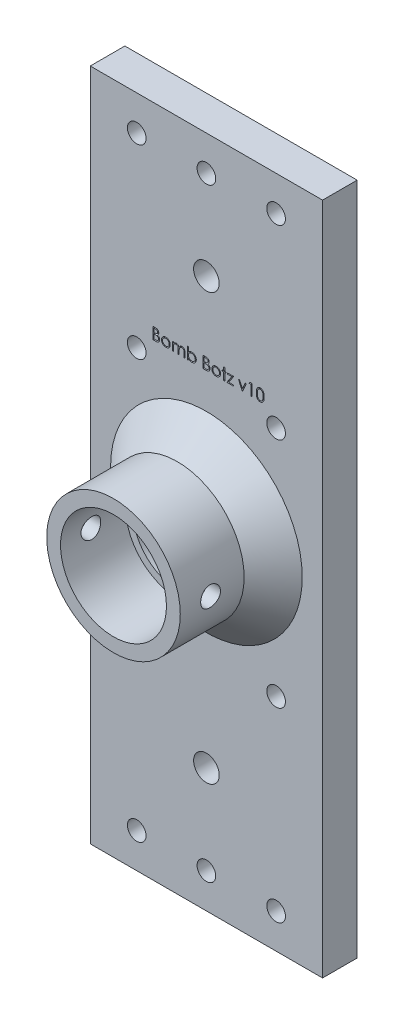
SolidWorks part; units mm, degrees
ref_plane "Front Plane" through (0, 0, 0) normal (0, 0, 1) x (1, 0, 0)
ref_plane "Top Plane" through (0, 0, 0) normal (0, 1, 0) x (1, 0, 0)
ref_plane "Right Plane" through (0, 0, 0) normal (1, 0, 0) x (0, 0, -1)
sketch "Sketch1" plane through (0, 0, 0) normal (0, 0, 1) x (1, 0, 0)
  line L5 (-31.75, 92.075) -> (31.75, 92.075)
  line L6 (-31.75, 92.075) -> (-31.75, -92.075)
  line L7 (-31.75, -92.075) -> (31.75, -92.075)
  line L8 (31.75, 92.075) -> (31.75, -92.075)
  line L9 (-31.75, 92.075) -> (31.75, -92.075) construction
  line L10 (-31.75, -92.075) -> (31.75, 92.075) construction
  point P5 (0, 0)
  dimension "D1" = 63.5
  dimension "D2" = 184.15
extrude "Boss-Extrude1" add sketch "Sketch1" along normal blind 4.7625 and the other way blind 4.699
sketch "Sketch3" plane through (0, 0, 4.7625) normal (0, 0, 1) x (1, 0, 0)
  circle A0 centre (0, 0) radius 6.35
  dimension "D1" = 12.7
extrude "Cut-Extrude1" cut sketch "Sketch3" against normal blind 0.508
sketch "Sketch4" plane through (0, 0, 4.7625) normal (0, 0, 1) x (1, 0, 0)
  circle A0 centre (0, 0) radius 18.2562
  dimension "D1" = 36.5125
extrude "Boss-Extrude2" add sketch "Sketch4" along normal blind 38.1 contours A0
sketch "Sketch5" plane through (0, 0, 42.8625) normal (0, 0, 1) x (1, 0, 0)
  circle A0 centre (0, 0) radius 12.4619
  dimension "D1" = 24.9237
extrude "Cut-Extrude2" cut sketch "Sketch5" against normal blind 38.1 contours A0
sketch "Sketch7" plane through (0, 0, 42.8625) normal (0, 0, 1) x (1, 0, 0)
  circle A0 centre (0, 0) radius 14.2875
  dimension "D1" = 28.575
extrude "Cut-Extrude3" cut sketch "Sketch7" against normal blind 30.48
hole_wizard "#10 Clearance Hole1" positions "Sketch8" profile "Sketch9" hole size "#10" standard "ANSI Inch" end condition up to next
sketch "Sketch8" plane through (0, 0, 4.7625) normal (0, 0, 1) x (1, 0, 0)
  line L0 (31.75, 92.075) -> (-31.75, 92.075) construction
  line L1 (31.75, -92.075) -> (31.75, 92.075) construction
  line L2 (-31.75, 92.075) -> (-31.75, -92.075) construction
  line L3 (-31.75, -92.075) -> (31.75, -92.075) construction
  point P0 (-19.05, 82.55)
  point P2 (-19.05, -82.55)
  point P4 (19.05, -82.55)
  point P6 (19.05, 82.55)
  point P23 (-19.05, 31.75)
  point P26 (-19.05, -31.75)
  point P28 (19.05, -31.75)
  point P30 (19.05, 31.75)
  point P31 (0, 82.55)
  point P33 (0, -82.55)
  dimension "D1" = 9.525
  dimension "D2" = 12.7
  dimension "D3" = 9.525
  dimension "D4" = 12.7
  dimension "D5" = 9.525
  dimension "D6" = 12.7
  dimension "D7" = 12.7
  dimension "D8" = 9.525
  dimension "D11" = 50.8
  dimension "D12" = 50.8
  dimension "D13" = 50.8
  dimension "D14" = 50.8
sketch "Sketch9" plane through (-19.05, 82.55, 4.7625) normal (1, 0, 0) x (0, -1, 0)
  line L0 (0, 0) -> (0, 9.4615)
  line L1 (0, 9.4615) -> (2.5527, 9.4615)
  line L2 (2.5527, 9.4615) -> (2.5527, 0)
  line L5 (2.5527, 0) -> (0, 0)
  line L11 (0, -6.35) -> (0, 107.95) construction
  dimension "Thru Hole Dia." = 5.1054
  dimension "Thru Hole Depth" = 9.4615
sketch "Sketch10" plane through (0, 0, 4.7625) normal (0, 0, 1) x (1, 0, 0)
  line L0 (31.75, 41.275) -> (-31.75, 41.275)
  line L1 (31.75, -92.075) -> (31.75, 92.075) construction
  line L2 (-31.75, 92.075) -> (-31.75, -92.075) construction
  line L3 (31.75, -41.275) -> (-31.75, -41.275)
  point P8 (-31.75, 0)
  dimension "D1" = 41.275
  dimension "D2" = 41.275
sketch "Sketch13" plane through (0, 0, 42.8625) normal (0, 0, 1) x (1, 0, 0)
  circle A0 centre (0, 0) radius 14.478
  dimension "D1" = 28.956
extrude "Cut-Extrude4" cut sketch "Sketch13" against normal up to surface (30.48 mm away) up to face at (14.2875, 0, 12.3825)
sketch "Sketch14" plane through (0, 0, 42.8625) normal (0, 0, 1) x (1, 0, 0)
  circle A0 centre (0, 0) radius 18.2562
extrude "Cut-Extrude5" cut sketch "Sketch14" against normal blind 12.7
sketch "Sketch15" plane through (0, -92.075, 0) normal (0, -1, 0) x (-1, 0, 0)
hole_wizard "#3 (0.213) Diameter Hole1" positions "3DSketch7" profile "Sketch22" hole size "#3" standard "ANSI Inch" end condition through all
sketch3d "3DSketch7"
  point P0 (18.2562, 0, 21.8735)
sketch "Sketch22" plane through (18.2562, 0, 21.8735) normal (0, 1, 0) x (0, 0, -1)
  line L0 (0, 0) -> (0, 50.0063)
  line L1 (0, 50.0063) -> (2.7051, 50.0063)
  line L2 (2.7051, 50.0063) -> (2.7051, 0)
  line L5 (2.7051, 0) -> (0, 0)
  line L11 (0, -6.35) -> (0, 107.95) construction
  dimension "Thru Hole Dia." = 5.4102
  dimension "Thru Hole Depth" = 50.0063
hole_wizard "CBORE for M6 Hex Head Bolt1" positions "Sketch25" profile "Sketch26" counterbore size "M6" standard "ANSI Metric" end condition through all
sketch "Sketch25" plane through (0, 0, -4.699) normal (0, 0, -1) x (-1, 0, 0)
  line L0 (-31.75, 41.275) -> (31.75, 41.275) construction
  line L1 (-31.75, -41.275) -> (31.75, -41.275) construction
  point P0 (0, -58.2083)
  point P2 (0, 58.2083)
  dimension "D1" = 16.9333
  dimension "D2" = 16.9333
sketch "Sketch26" plane through (0, -58.2083, -4.699) normal (1, 0, 0) x (0, 1, 0)
  line L0 (0, 0) -> (0, 34.8615)
  line L1 (0, 34.8615) -> (3.5, 34.8615)
  line L3 (3.5, 34.8615) -> (3.5, 4.38)
  line L4 (3.5, 4.38) -> (7.275, 4.38)
  line L5 (7.275, 4.38) -> (7.275, 0)
  line L7 (7.275, 0) -> (0, 0)
  line L11 (0, -6.35) -> (0, 107.95) construction
  dimension "Thru Hole Dia." = 7
  dimension "Thru Hole Depth" = 34.8615
  dimension "C'Bore Dia." = 14.55
  dimension "C'Bore Depth" = 4.38
sketch "Sketch28" plane through (0, 0, 4.7625) normal (0, 0, 1) x (1, 0, 0)
  text T0 "Bomb Botz v10"
extrude "Boss-Extrude4" add sketch "Sketch28" against normal blind 1.27
chamfer "Chamfer1" distance 7.9375 distance2 7.9375 1 edges at (18.2562, 0, 4.7625)
sketch "Sketch29" plane through (0, 0, 4.7625) normal (0, 0, 1) x (1, 0, 0)
  text T0 "Bomb Botz v10"
extrude "Cut-Extrude6" cut sketch "Sketch29" against normal blind 1.27
